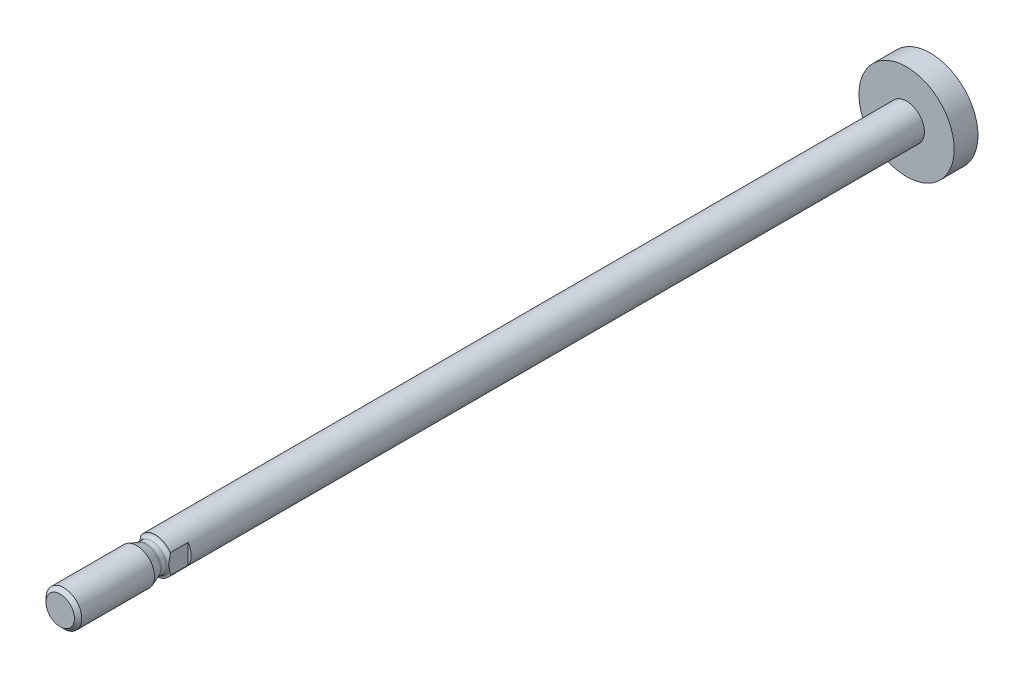
SolidWorks part; units mm, degrees
ref_plane "Ebene vorne" through (0, 0, 0) normal (0, 0, 1) x (1, 0, 0)
ref_plane "Ebene oben" through (0, 0, 0) normal (0, 1, 0) x (1, 0, 0)
ref_plane "Ebene rechts" through (0, 0, 0) normal (1, 0, 0) x (0, 0, -1)
sketch "Skizze1" plane through (0, 0, 0) normal (1, 0, 0) x (0, 0, -1)
  line L0 (-5, 0) -> (-5, 3)
  line L1 (-5, 3) -> (121.2, 3)
  line L2 (121.2, 3) -> (121.2, 8)
  line L3 (121.2, 8) -> (125.2, 8)
  line L4 (125.2, 8) -> (125.2, 0)
  line L5 (125.2, 0) -> (-5, 0)
  line L6 (125.2, 0) -> (-5, 0) construction
revolve "Rotation1" add sketch "Skizze1" angle 360 about L6 reverse direction yes
sketch "Skizze2" plane through (0, 0, 0) normal (1, 0, 0) x (0, 0, -1)
  line L0 (-21, 0) -> (-21, 2.3865)
  line L1 (-21, 2.3865) -> (-20.3865, 3)
  line L2 (-20.3865, 3) -> (-8.1485, 3)
  line L3 (-8.1485, 3) -> (-6.5994, 2.4362)
  line L4 (-6.3942, 2.4) -> (-5.6, 2.4)
  line L5 (-5, 3) -> (-4, 3)
  line L6 (-4, 3) -> (-4, 0)
  line L7 (-4, 0) -> (-21, 0)
  line L8 (-4, 0) -> (-21, 0) construction
  arc A0 (-6.5994, 2.4362) -> (-6.3942, 2.4) centre (-6.3942, 3) ccw
  arc A1 (-5.6, 2.4) -> (-5, 3) centre (-5.6, 3) ccw
revolve "Rotation2" add sketch "Skizze2" angle 360 about L8 reverse direction yes
cosmetic thread "Gewindedarstellung1" parameters "D1"=12.8515, "D2"=4.773
ref_plane "Ebene1" through (0, 0, 5) normal (0, 0, 1) x (1, 0, 0)
ref_plane "Ebene2" through (0, 0, 2) normal (0, 0, 1) x (1, 0, 0)
sketch "Skizze3" plane through (0, 0, 2) normal (0, 0, 1) x (1, 0, 0)
  line L0 (-5, 10) -> (-5, -5)
  line L1 (-5, -5) -> (-2.5, -5)
  line L2 (-2.5, -5) -> (-2.5, 5)
  line L3 (-2.5, 5) -> (2.5, 5)
  line L4 (2.5, 5) -> (2.5, -5)
  line L5 (2.5, -5) -> (5, -5)
  line L6 (5, -5) -> (5, 10)
  line L7 (5, 10) -> (-5, 10)
extrude "Schnitt-Linear austragen1" cut sketch "Skizze3" along normal blind 4
ref_plane "Ebene3" through (0, 0, -255) normal (0, 0, 1) x (1, 0, 0)
ref_plane "Ebene4" through (0, 0, 16) normal (0, 0, 1) x (1, 0, 0)
ref_plane "Ebene5" through (0, 0, 11.2) normal (0, 0, 1) x (1, 0, 0)
ref_plane "FDT_KSAUFSATZ XY" through (0, 0, 11.2) normal (0, 0, 1) x (1, 0, 0)
ref_plane "FDT_KSAUFSATZ XZ" through (0, 0, 0) normal (0, 1, 0) x (1, 0, 0)
ref_plane "FDT_KSAUFSATZ YZ" through (0, 0, 0) normal (-1, 0, 0) x (0, 0, 1)
ref_axis "FDT_KSAUFSATZ X" through (80.9, 0, 11.2) along (-1, 0, 0)
ref_axis "FDT_KSAUFSATZ Y" through (0, 50, 11.2) along (0, -1, 0)
ref_axis "FDT_KSAUFSATZ Z" through (0, 0, 80.9) along (0, 0, -1)
sketch3d "FDT_KSAUFSATZ"
  point P0 (0, 0, 11.2)
ref_plane "FDT_NUT XY" through (0, 0, 11.2) normal (0, 0, 1) x (1, 0, 0)
ref_plane "FDT_NUT XZ" through (0, 0, 0) normal (0, 1, 0) x (1, 0, 0)
ref_plane "FDT_NUT YZ" through (0, 0, 0) normal (-1, 0, 0) x (0, 0, 1)
ref_axis "FDT_NUT X" through (80.9, 0, 11.2) along (-1, 0, 0)
ref_axis "FDT_NUT Y" through (0, 50, 11.2) along (0, -1, 0)
ref_axis "FDT_NUT Z" through (0, 0, 80.9) along (0, 0, -1)
sketch3d "FDT_NUT"
  point P0 (0, 0, 11.2)
ref_plane "KS XY" through (0, 0, 0) normal (0, 0, -1) x (-1, 0, 0)
ref_plane "KS XZ" through (0, 0, 0) normal (0, 1, 0) x (1, 0, 0)
ref_plane "KS YZ" through (0, 0, 0) normal (1, 0, 0) x (0, 0, -1)
ref_axis "KS X" through (-80.9, 0, 0) along (1, 0, 0)
ref_axis "KS Y" through (0, 50, 0) along (0, -1, 0)
ref_axis "KS Z" through (0, 0, -80.9) along (0, 0, 1)
sketch3d "KS"
  point P0 (0, 0, 0)
ref_plane "NUT1 XY" through (0, 0, 16) normal (0, 0, 1) x (1, 0, 0)
ref_plane "NUT1 XZ" through (0, 0, 0) normal (0, -1, 0) x (-1, 0, 0)
ref_plane "NUT1 YZ" through (0, 0, 0) normal (1, 0, 0) x (0, 0, -1)
ref_axis "NUT1 X" through (-80.9, 0, 16) along (1, 0, 0)
ref_axis "NUT1 Y" through (0, -50, 16) along (0, 1, 0)
ref_axis "NUT1 Z" through (0, 0, 80.9) along (0, 0, -1)
sketch3d "NUT1"
  point P0 (0, 0, 16)
